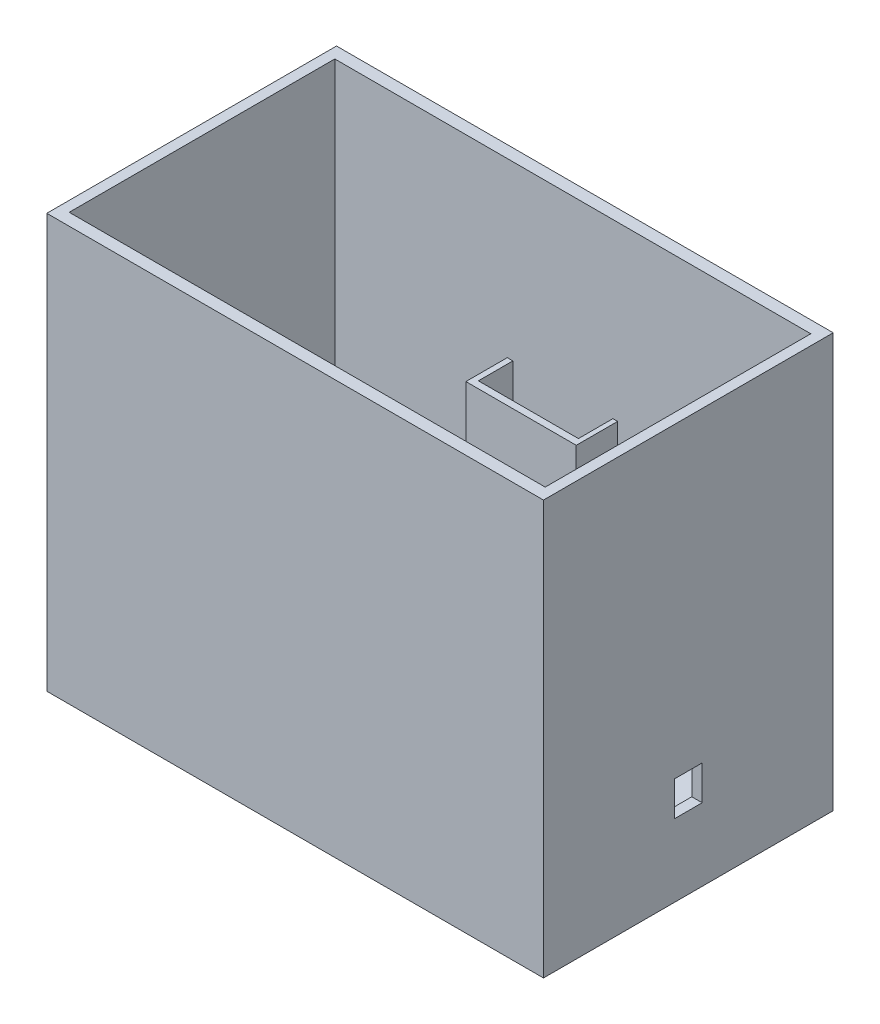
SolidWorks part; units mm, degrees
ref_plane "Front Plane" through (0, 0, 0) normal (0, 0, 1) x (1, 0, 0)
ref_plane "Top Plane" through (0, 0, 0) normal (0, 1, 0) x (1, 0, 0)
ref_plane "Right Plane" through (0, 0, 0) normal (1, 0, 0) x (0, 0, -1)
ref_plane "Plane1" through (0, 0, 0) normal (0, 1, 0) x (1, 0, 0)
sketch "Sketch1" plane through (0, 0, 0) normal (0, 1, 0) x (1, 0, 0)
  line L1 (-72, -42) -> (72, -42)
  line L2 (-72, -42) -> (-72, 42)
  line L3 (-72, 42) -> (72, 42)
  line L4 (72, -42) -> (72, 42)
  line L5 (-72, -42) -> (72, 42) construction
  line L6 (-72, 42) -> (72, -42) construction
  point P0 (0, 0)
  dimension "D1" = 144
  dimension "D2" = 84
extrude "Boss-Extrude1" add sketch "Sketch1" along normal blind 120
sketch "Sketch2" plane through (0, 120, 0) normal (0, 1, 0) x (1, 0, 0)
  line L1 (-69, -38.5) -> (69, -38.5)
  line L2 (-69, -38.5) -> (-69, 38.5)
  line L3 (-69, 38.5) -> (69, 38.5)
  line L4 (69, -38.5) -> (69, 38.5)
  line L5 (-69, -38.5) -> (69, 38.5) construction
  line L6 (-69, 38.5) -> (69, -38.5) construction
  point P0 (0, 0)
  dimension "D1" = 138
  dimension "D2" = 77
extrude "Cut-Extrude1" cut sketch "Sketch2" against normal blind 100
sketch "Sketch3" plane through (-72, 0, 0) normal (-1, 0, 0) x (0, 0, 1)
  line L1 (-42, 0) -> (42, 0) construction
  line L2 (42, 120) -> (42, 0) construction
  circle A0 centre (-25, 24) radius 4
  dimension "D1" = 8
  dimension "D2" = 24
  dimension "D3" = 67
extrude "Cut-Extrude3" cut sketch "Sketch3" against normal mid plane 100
ref_plane "Plane2" through (0, 25, 0) normal (0, 1, 0) x (1, 0, 0)
sketch "Sketch4" plane through (0, 25, 0) normal (0, 1, 0) x (1, 0, 0)
  line L0 (69, 38.5) -> (-69, 38.5) construction
  line L2 (-19, 38.5) -> (-19, 26.5)
  line L3 (-19, 26.5) -> (13, 26.5)
  line L4 (13, 38.5) -> (13, 26.5)
  line L5 (-69, 38.5) -> (-69, -38.5) construction
  line L6 (-19, 38.5) -> (13, 38.5)
  dimension "D1" = 12
  dimension "D2" = 32
  dimension "D3" = 50
ref_plane "Plane3" through (0, 20, 0) normal (0, 1, 0) x (1, 0, 0)
sketch "Sketch5" plane through (72, 0, 0) normal (1, 0, 0) x (0, 0, -1)
  line L6 (-4, 31) -> (4, 31)
  line L7 (-4, 31) -> (-4, 21)
  line L8 (-4, 21) -> (4, 21)
  line L9 (4, 31) -> (4, 21)
  line L10 (-4, 31) -> (4, 21) construction
  line L11 (-4, 21) -> (4, 31) construction
  line L12 (42.35, 20) -> (-42.35, 20) construction
  point P0 (0, 26)
  dimension "D1" = 10
  dimension "D2" = 8
  dimension "D3" = 6
extrude "Cut-Extrude4" cut sketch "Sketch5" against normal mid plane 40
ref_plane "Plane4" through (0, 0, 0) normal (0, 1, 0) x (1, 0, 0)
extrude "Boss-Extrude4" add sketch "Sketch4" along normal blind 45
extrude "Boss-Extrude5" add sketch "Sketch4<2>" along normal blind 45
sketch "Sketch4<2>" plane through (0, 25, 0) normal (0, 1, 0) x (1, 0, 0) same geometry as "Sketch4"
sketch "Sketch11" plane through (0, 70, 0) normal (0, 1, 0) x (1, 0, 0)
  line L0 (-19, 38.5) -> (13, 38.5) construction
  line L1 (11.6266, 38.5) -> (-17.3734, 38.5)
  line L2 (11.6266, 38.5) -> (11.6266, 28.5)
  line L3 (11.6266, 28.5) -> (-17.3734, 28.5)
  line L4 (-17.3734, 38.5) -> (-17.3734, 28.5)
  line L5 (11.6266, 38.5) -> (-17.3734, 28.5) construction
  line L6 (11.6266, 28.5) -> (-17.3734, 38.5) construction
  point P0 (-2.8734, 33.5)
  dimension "D1" = 10
  dimension "D2" = 29
extrude "Cut-Extrude5" cut sketch "Sketch11" against normal blind 45
